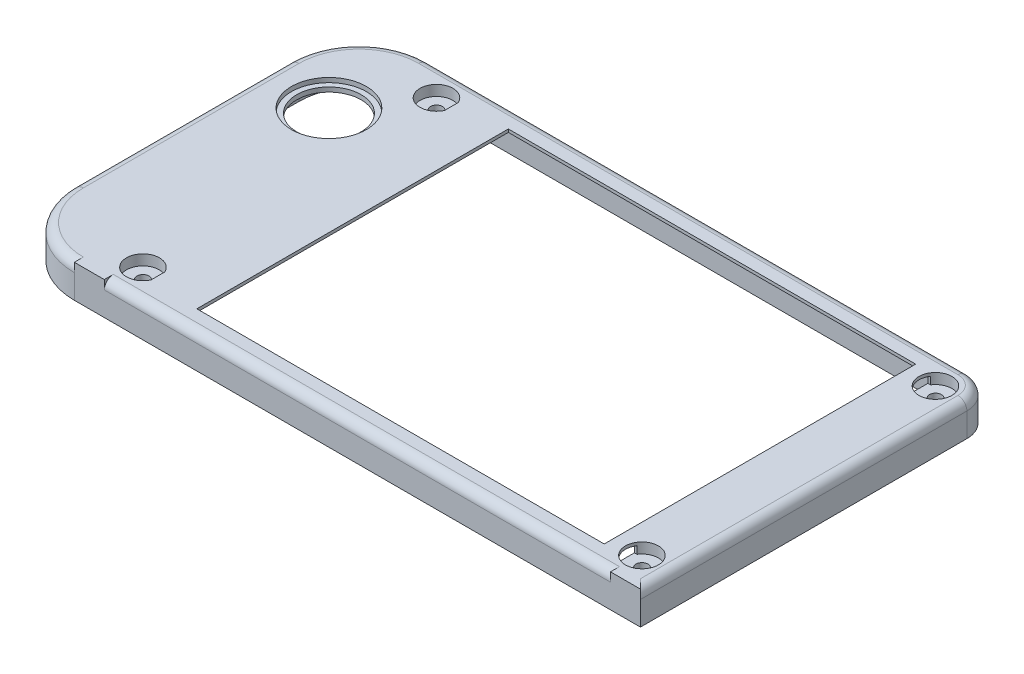
SolidWorks part; units mm, degrees
material "ABS"
ref_plane "Front Plane" through (0, 0, 0) normal (0, 0, 1) x (1, 0, 0)
ref_plane "Top Plane" through (0, 0, 0) normal (0, 1, 0) x (1, 0, 0)
ref_plane "Right Plane" through (0, 0, 0) normal (1, 0, 0) x (0, 0, -1)
sketch "Sketch2" plane through (0, 0, 0) normal (0, 1, 0) x (1, 0, 0)
  line L0 (-53, -18) -> (-53, 18)
  line L1 (-41.5, -28) -> (-41.05, -28)
  line L2 (-51.5, -18) -> (-51.5, 18)
  line L3 (-41.5, 28) -> (-41.05, 28)
  line L4 (51.5, -18.5) -> (51.5, 18.5)
  line L5 (-51.5, -28) -> (51.5, 28) construction
  line L6 (-51.5, 28) -> (51.5, -28) construction
  line L7 (-41.5, 29.5) -> (53, 29.5)
  line L8 (53, -29.5) -> (53, 29.5)
  line L9 (-41.5, -29.5) -> (53, -29.5)
  line L10 (-51.5, -28) -> (51.5, -28) construction
  line L11 (-35.05, -24.5) -> (48.25, -24.5) construction
  line L12 (-35.05, -24.5) -> (-35.05, 24.5) construction
  line L13 (-35.05, 24.5) -> (48.25, 24.5) construction
  line L14 (48.25, -24.5) -> (48.25, 24.5) construction
  line L15 (-35.05, -24.5) -> (48.25, 24.5) construction
  line L16 (-35.05, 24.5) -> (48.25, -24.5) construction
  line L17 (-51.5, -28) -> (-51.5, 28) construction
  line L18 (-51.5, 28) -> (51.5, 28) construction
  line L19 (-53, -29.5) -> (-53, 29.5) construction
  line L20 (-53, -29.5) -> (53, -29.5) construction
  line L21 (-53, 29.5) -> (53, 29.5) construction
  line L22 (45.5, 28) -> (45.5, 22.3349)
  line L23 (45.5, -22.3349) -> (45.5, -28)
  line L24 (-32.55, 28) -> (-32.55, 22.0505)
  line L25 (-32.55, -22.0505) -> (-32.55, -28)
  line L26 (-38.55, 24.5) -> (-38.55, 25.5)
  line L27 (-32.55, 28) -> (45.5, 28)
  line L28 (-32.55, -28) -> (45.5, -28)
  line L29 (-38.55, -24.5) -> (-38.55, -25.5)
  line L30 (48.25, -21) -> (49, -21)
  line L31 (48.25, 21) -> (49, 21)
  line L33 (51.5, -28) -> (51.5, 28) construction
  line L35 (-32.55, 26) -> (-32.55, 23)
  line L36 (-32.55, -23) -> (-32.55, -26)
  line L37 (45.5, 26) -> (45.9451, 26)
  line L38 (45.5, 23) -> (45.9451, 23)
  line L39 (45.5, -23) -> (45.9451, -23)
  line L40 (45.5, -26) -> (45.9451, -26)
  line L41 (45.5, -23) -> (45.5, -26)
  line L42 (45.5, 26) -> (45.5, 23)
  line L43 (-32.7451, 26) -> (-32.55, 26)
  line L44 (-32.55, 23) -> (-32.7451, 23)
  line L45 (-32.55, -23) -> (-32.7451, -23)
  line L46 (-32.55, -26) -> (-32.7451, -26)
  line L47 (-51.5, -18) -> (-51.5, 18)
  line L48 (-41.5, 28) -> (51.5, 28)
  line L49 (51.5, -28) -> (51.5, 28)
  line L50 (-41.5, -28) -> (51.5, -28)
  arc A0 (-41.5, -28) -> (-51.5, -18) centre (-41.5, -18) cw
  arc A1 (-51.5, 18) -> (-41.5, 28) centre (-41.5, 18) cw
  arc A2 (-53, -18) -> (-41.5, -29.5) centre (-41.5, -18) ccw
  arc A3 (-53, 18) -> (-41.5, 29.5) centre (-41.5, 18) cw
  arc A4 (-38.55, 24.5) -> (-32.55, 22.0505) centre (-35.05, 24.5) ccw
  arc A5 (45.5, 22.3349) -> (48.25, 21) centre (48.25, 24.5) ccw
  arc A6 (48.25, -21) -> (45.5, -22.3349) centre (48.25, -24.5) ccw
  arc A7 (-32.55, -22.0505) -> (-38.55, -24.5) centre (-35.05, -24.5) ccw
  circle A8 centre (-35.05, 24.5) radius 1
  circle A9 centre (48.25, 24.5) radius 1
  circle A10 centre (48.25, -24.5) radius 1
  circle A11 centre (-35.05, -24.5) radius 1
  arc A12 (-32.7451, 26) -> (-32.7451, 23) centre (-35.05, 24.5) ccw
  arc A13 (45.9451, 23) -> (45.9451, 26) centre (48.25, 24.5) ccw
  arc A15 (-32.7451, -23) -> (-32.7451, -26) centre (-35.05, -24.5) ccw
  arc A16 (-38.55, 25.5) -> (-41.05, 28) centre (-41.05, 25.5) ccw
  arc A17 (-38.55, -25.5) -> (-41.05, -28) centre (-41.05, -25.5) cw
  arc A18 (49, -21) -> (51.5, -18.5) centre (49, -18.5) ccw
  arc A19 (49, 21) -> (51.5, 18.5) centre (49, 18.5) cw
  arc A20 (45.9451, -26) -> (45.9451, -23) centre (48.25, -24.5) ccw
  arc A21 (-51.5, 18) -> (-41.5, 28) centre (-41.5, 18) cw
  arc A22 (-51.5, -18) -> (-41.5, -28) centre (-41.5, -18) ccw
  point P0 (0, 0)
  point P10 (6.6, 0)
  dimension "D7" = 10
  dimension "D8" = 11.5
  dimension "D9" = 7
  dimension "D10" = 2
  dimension "D11" = 5.5
  dimension "D14" = 2.5
  dimension "D1" = 103
  dimension "D2" = 56
  dimension "D4" = 83.3
  dimension "D5" = 49
  dimension "D6" = 3.25
  dimension "D12" = 2.75
  dimension "D13" = 2.5
  dimension "D15" = 1.5
  dimension "D16" = 1.5
  dimension "D3" = 1.5
  dimension "D17" = 1.5
extrude "Boss-Extrude1" add sketch "Sketch2" against normal blind 1.5 contours L9 L8 L7 A3 L0 A2
extrude "Boss-Extrude2" add sketch "Sketch2<3>" against normal blind 4 from surface contours A3 L0 A2 L9 L8 L7 A6 L4 L1 A0 L2 A1 L3 A5 region at (-51.7869, 0, 0) starting at face at (-14.6272, -1.5, 0)
sketch "Sketch2<3>" plane through (0, 0, 0) normal (0, 1, 0) x (1, 0, 0) same geometry as "Sketch2"
extrude "Boss-Extrude3" add sketch "Sketch2<4>" against normal offset from surface (2.25 mm away) 1.75 from surface contours A20 L40 L23 L50 L49 A18 L30 A6 L39 | L31 A19 L49 L48 L22 L37 A13 L38 A5 | L29 A17 L50 L25 L46 A15 L45 A7 | A16 L26 A4 L24 L44 A12 L43 L48 region at (-39.2044, 0, 27.3456) region at (45.6124, 0, 27) region at (-36.8, 0, -27.8899) region at (50.8472, 0, -20.3472) up to face at (-14.5237, -5.5, 0) starting at face at (-14.5237, -1.5, 0)
sketch "Sketch2<4>" plane through (0, 0, 0) normal (0, 1, 0) x (1, 0, 0) same geometry as "Sketch2"
extrude "Boss-Extrude4" add sketch "Sketch2<5>" along normal blind 2 from surface contours L45 A15 L46 L25 A11 | L43 A12 L44 L24 A8 | L38 A13 L37 L22 A9 | L40 A20 L39 L23 A10 region at (-32.6476, 0, 25.924) region at (45.5778, 0, 24.5) region at (-32.626, 0, -24.5) region at (45.7226, 0, -25.9222) starting at face at (-35.4667, -3.75, 24.9503)
sketch "Sketch2<5>" plane through (0, 0, 0) normal (0, 1, 0) x (1, 0, 0) same geometry as "Sketch2"
extrude "Cut-Extrude2" cut sketch "Sketch2<7>" along normal up to next from surface contours L45 A15 L46 L25 A11 | A11 | L43 A12 L44 L24 A8 | A8 | L38 A13 L37 L22 A9 | A9 | L40 A20 L39 L23 A10 | A10 region at (-32.6476, 0, 25.924) region at (45.5778, 0, 24.5) region at (-32.626, 0, -24.5) region at (45.7226, 0, -25.9222) region at (-35.05, 0, -24.5) region at (48.25, 0, -24.5) region at (48.25, 0, 24.5) region at (-35.05, 0, 24.5) starting at face at (0.6894, -1.5, 0)
sketch "Sketch2<7>" plane through (0, 0, 0) normal (0, 1, 0) x (1, 0, 0) same geometry as "Sketch2"
sketch "Sketch4" plane through (0, -1.5, 0) normal (0, -1, 0) x (1, 0, 0)
  line L0 (-32.55, -28) -> (-32.55, -22.0505) construction
  line L1 (-32.55, 22.0505) -> (-32.55, 28) construction
  line L2 (-35.05, 24.5) -> (-35.05, -24.5) construction
  line L3 (45.5, 22.3349) -> (45.5, 28) construction
  line L4 (-35.05, 24.5) -> (48.25, 24.5) construction
  line L5 (45.5, -28) -> (45.5, -22.3349) construction
  line L6 (48.25, 24.5) -> (48.25, -24.5) construction
  line L7 (-35.05, -24.5) -> (48.25, -24.5) construction
  line L8 (-32.55, -28) -> (-32.55, -22.0505) construction
  line L9 (-32.55, 22.0505) -> (-32.55, 28) construction
  line L10 (-35.05, 24.5) -> (-35.05, -24.5) construction
  line L11 (45.5, 22.3349) -> (45.5, 28) construction
  line L12 (-35.05, 24.5) -> (48.25, 24.5) construction
  line L13 (45.5, -28) -> (45.5, -22.3349) construction
  line L14 (48.25, 24.5) -> (48.25, -24.5) construction
  line L15 (-35.05, -24.5) -> (48.25, -24.5) construction
  line L17 (45.5, -28) -> (-32.55, -28)
  line L18 (45.5, -28) -> (45.5, 28)
  line L19 (45.5, 28) -> (-32.55, 28)
  line L20 (-32.55, -28) -> (-32.55, 28)
  line L21 (45.5, -28) -> (-32.55, 28) construction
  line L22 (45.5, 28) -> (-32.55, -28) construction
  line L23 (-24.55, -26) -> (43.45, -26)
  line L24 (-24.55, -26) -> (-24.55, 26)
  line L25 (-24.55, 26) -> (43.45, 26)
  line L26 (43.45, -26) -> (43.45, 26)
  line L27 (-24.55, -26) -> (43.45, 26) construction
  line L28 (-24.55, 26) -> (43.45, -26) construction
  point P8 (6.475, 0)
  point P16 (9.45, 0)
  dimension "D1" = 68
  dimension "D2" = 56
  dimension "D3" = 52
  dimension "D4" = 8
extrude "Cut-Extrude3" cut sketch "Sketch4" against normal up to next contours L23 L26 L25 L24
extrude "Cut-Extrude4" cut sketch "Sketch4<3>" against normal offset from surface (1 mm away) 0.5 from surface contours L20 L19 L18 L17 up to face at (46.9863, 0, -24.5) starting at face at (-0.7882, -1.5, 0)
sketch "Sketch4<3>" plane through (0, -1.5, 0) normal (0, -1, 0) x (1, 0, 0) same geometry as "Sketch4"
sketch "Sketch5" plane through (0, 0, 0) normal (0, 1, 0) x (1, 0, 0)
  line L0 (-32.55, 26) -> (-32.55, 23) construction
  line L1 (-32.55, 26) -> (-32.55, 23) construction
  line L2 (45.5, 26) -> (45.5, 23) construction
  line L3 (45.5, 26) -> (45.5, 23) construction
  line L4 (45.5, -23) -> (45.5, -26) construction
  line L5 (45.5, -23) -> (45.5, -26) construction
  line L6 (-32.55, -23) -> (-32.55, -26) construction
  line L7 (-32.55, -23) -> (-32.55, -26) construction
  arc A0 (-32.7451, 26) -> (-32.7451, 23) centre (-35.05, 24.5) ccw construction
  arc A1 (-32.7451, 26) -> (-32.7451, 23) centre (-35.05, 24.5) ccw construction
  arc A2 (45.9451, 23) -> (45.9451, 26) centre (48.25, 24.5) ccw construction
  arc A3 (45.9451, 23) -> (45.9451, 26) centre (48.25, 24.5) ccw construction
  arc A4 (45.9451, -26) -> (45.9451, -23) centre (48.25, -24.5) ccw construction
  arc A5 (45.9451, -26) -> (45.9451, -23) centre (48.25, -24.5) ccw construction
  arc A6 (-32.7451, -23) -> (-32.7451, -26) centre (-35.05, -24.5) ccw construction
  arc A7 (-32.7451, -23) -> (-32.7451, -26) centre (-35.05, -24.5) ccw construction
  circle A10 centre (-35.05, 24.5) radius 2.75
  circle A11 centre (48.25, 24.5) radius 2.75
  circle A12 centre (48.25, -24.5) radius 2.75
  circle A13 centre (-35.05, -24.5) radius 2.75
  circle A14 centre (-35.05, -24.5) radius 2.9155
  circle A15 centre (48.25, -24.5) radius 3.1325
  circle A16 centre (48.25, 24.5) radius 3.1325
  circle A17 centre (-35.05, 24.5) radius 2.9155
  line M1 (45.5, 26) -> (45.9451, 26)
  arc M2 (45.9451, 26) -> (45.9451, 23) centre (48.25, 24.5) cw
  line M3 (45.9451, 23) -> (45.5, 23)
  line M4 (45.5, 23) -> (45.5, 26)
  line M5 (-32.55, -26) -> (-32.7451, -26)
  arc M6 (-32.7451, -26) -> (-32.7451, -23) centre (-35.05, -24.5) cw
  line M7 (-32.7451, -23) -> (-32.55, -23)
  line M8 (-32.55, -23) -> (-32.55, -26)
  line M15 (-32.55, 23) -> (-32.7451, 23)
  arc M16 (-32.7451, 23) -> (-32.7451, 26) centre (-35.05, 24.5) cw
  line M17 (-32.7451, 26) -> (-32.55, 26)
  line M18 (-32.55, 26) -> (-32.55, 23)
  line M19 (45.5, -23) -> (45.9451, -23)
  arc M20 (45.9451, -23) -> (45.9451, -26) centre (48.25, -24.5) cw
  line M21 (45.9451, -26) -> (45.5, -26)
  line M22 (45.5, -26) -> (45.5, -23)
extrude "Boss-Extrude5" add sketch "Sketch5" against normal up to vertex (0.5 mm away) contours A17 M17 M15 M16 | A17 A10 M18 | A10 M18 M17 | A10 M15 M18 | A11 M1 M4 | A11 M4 M3 | A16 M4 | A16 M3 M1 M2 | A12 M19 M22 | A15 M21 M19 M20 | A15 M22 | A12 M22 M21 | A14 M7 M5 M6 | A13 M5 M8 | A14 A13 M8 | A13 M8 M7 region at (-32.6132, 0, -25.8854) region at (-37.8796, 0, -24.5) region at (-32.6132, 0, -23.1146) region at (-32.5197, 0, -25.8228) region at (49.0568, 0, -27.2188) region at (45.6315, 0, -25.6313) region at (45.6315, 0, -23.3687) region at (45.3462, 0, -24.5) region at (49.0568, 0, 21.7812) region at (45.6315, 0, 23.3687) region at (45.6315, 0, 25.6313) region at (45.3462, 0, 24.5) region at (-32.6132, 0, 23.1146) region at (-37.8796, 0, 24.5) region at (-32.6132, 0, 25.8854) region at (-32.5197, 0, 23.1772) up to point (-32.55, -0.5, 23)
sketch "Sketch6" plane through (0, 0, 0) normal (0, 1, 0) x (1, 0, 0)
  line L0 (-35.05, 24.5) -> (48.25, 24.5) construction
  line L1 (-35.05, -24.5) -> (-35.05, 24.5) construction
  line L2 (-35.05, 24.5) -> (48.25, 24.5) construction
  line L3 (-35.05, -24.5) -> (-35.05, 24.5) construction
  line L4 (-41.5, 18) -> (-48.5711, 25.0711) construction
  line L5 (-42.55, 15.5027) -> (-42.55, 50015.5027) construction
  circle A0 centre (-42.55, 14.05) radius 5.375
  arc A5 (-41.5, 28) -> (-51.5, 18) centre (-41.5, 18) ccw construction
  arc A6 (-41.5, 28) -> (-51.5, 18) centre (-41.5, 18) ccw construction
  circle A7 centre (-42.55, 14.05) radius 6.25
  point P5 (-42.55, 19.05)
  dimension "D1" = 10.75
  dimension "D2" = 7.5
  dimension "D3" = 12.5
  dimension "D4" = 5
extrude "Cut-Extrude6" cut sketch "Sketch6" against normal up to next contours A0
extrude "Cut-Extrude7" cut sketch "Sketch6<4>" against normal blind 0.75 contours A7
sketch "Sketch6<4>" plane through (0, 0, 0) normal (0, 1, 0) x (1, 0, 0) same geometry as "Sketch6"
fillet "Fillet1" radius 1 18 edges at (-36.3729, -1.5, -21.2596) (-38.55, -1.5, -25) (-39.2822, -1.5, -27.2678) (-41.275, -1.5, -28) (-36.3729, -1.5, 21.2596) (-38.55, -1.5, 25) (-39.2822, -1.5, 27.2678) (-41.275, -1.5, 28) (46.7216, -1.5, 21.3514) (48.625, -1.5, 21) (50.7678, -1.5, 20.2678) (46.7216, -1.5, -21.3514) (48.625, -1.5, -21) (50.7678, -1.5, -20.2678) (-48.5711, -1.5, 25.0711) (-51.5, -1.5, 0) (-48.5711, -1.5, -25.0711) (51.5, -1.5, 0)
fillet "Fillet2" radius 1.5 6 edges at (5.75, 0, 29.5) (-49.6317, 0, 26.1317) (-53, 0, 0) (-49.6317, 0, -26.1317) (53, 0, 0) (5.75, 0, -29.5)
fillet "Fillet3" radius 4.5 2 edges at (52.5607, -0.4393, -29.0607) (53, -3.5, -29.5)
sketch "Sketch7" plane through (0, 0, 0) normal (1, 0, 0) x (0, 0, -1)
  line L0 (-28, 0) -> (25, 0) construction
  line L1 (-29.5, -5.5) -> (-28, -5.5)
  line L2 (-29.5, -5.5) -> (-29.5, 0)
  line L3 (-29.5, 0) -> (-28, 0)
  line L4 (-28, -5.5) -> (-28, 0)
  dimension "D1" = 1.5
extrude "Boss-Extrude6" add sketch "Sketch7" along normal blind 5 from vertex starting at point (-41.5, -1.5, 29.5)
ref_plane "Plane1" through (11.75, 0, -11.75) normal (0.7071, 0, -0.7071) x (-0.7071, 0, -0.7071)
extrude "Boss-Extrude7" add sketch "Sketch7<3>" along normal up to surface (5 mm away) from offset 48 contours L2 L3 L4 L1 up to plane "Plane1"
sketch "Sketch7<3>" plane through (0, 0, 0) normal (1, 0, 0) x (0, 0, -1) same geometry as "Sketch7"
